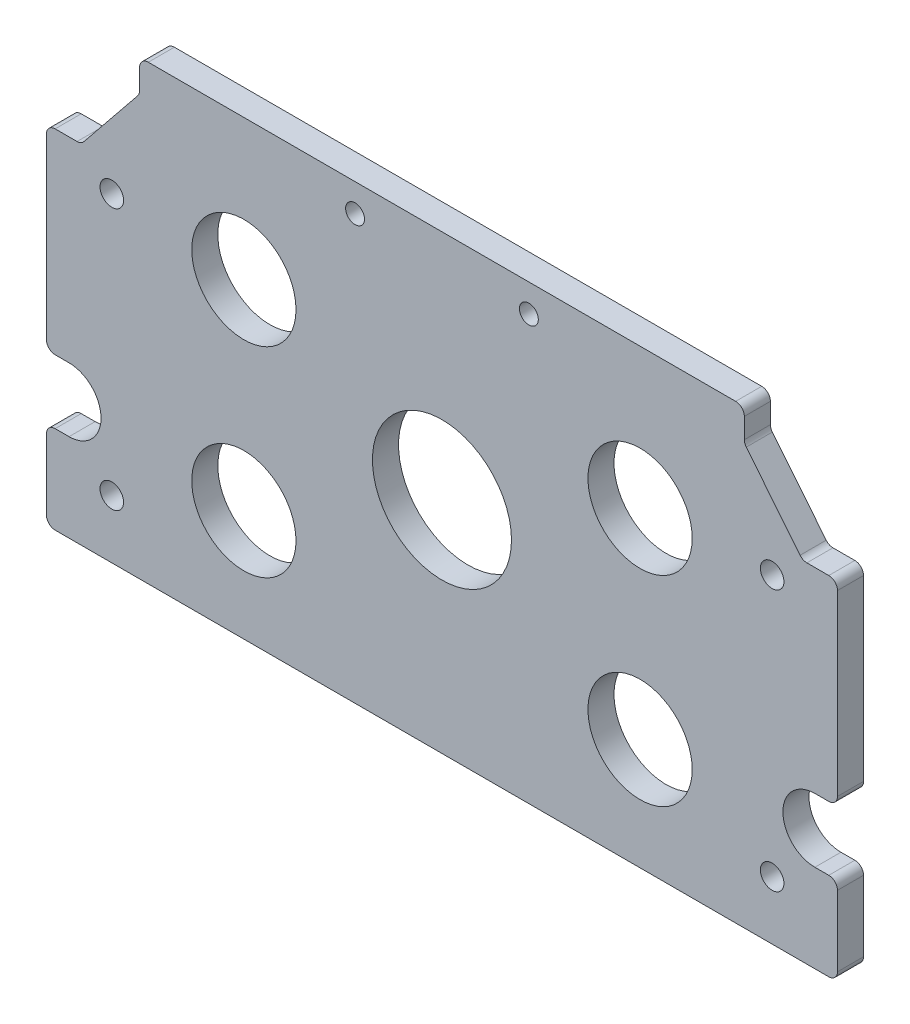
SolidWorks part; units mm, degrees
ref_plane "Front Plane" through (0, 0, 0) normal (0, 0, 1) x (1, 0, 0)
ref_plane "Top Plane" through (0, 0, 0) normal (0, 1, 0) x (1, 0, 0)
ref_plane "Right Plane" through (0, 0, 0) normal (1, 0, 0) x (0, 0, -1)
sketch "Sketch1" plane through (0, 0, 0) normal (0, 0, 1) x (1, 0, 0)
  line L32 (0.762, 54.483) -> (0.762, 41.5925)
  line L33 (2.3495, 40.005) -> (143.7005, 40.005)
  line L34 (145.288, 41.5925) -> (145.288, 54.483)
  line L35 (143.7005, 56.0705) -> (141.1605, 56.0705)
  line L36 (141.1605, 67.7545) -> (143.7005, 67.7545)
  line L37 (145.288, 69.342) -> (145.288, 101.9175)
  line L38 (143.7005, 103.505) -> (139.6964, 103.505)
  line L39 (138.4614, 104.095) -> (128.6225, 116.2765)
  line L40 (128.27, 117.274) -> (128.27, 120.9675)
  line L41 (126.6825, 122.555) -> (19.3675, 122.555)
  line L42 (17.78, 120.9675) -> (17.78, 117.274)
  line L43 (17.4275, 116.2765) -> (7.5886, 104.095)
  line L44 (6.3536, 103.505) -> (2.3495, 103.505)
  line L45 (0.762, 101.9175) -> (0.762, 69.342)
  line L46 (2.3495, 67.7545) -> (4.8895, 67.7545)
  line L47 (4.8895, 56.0705) -> (2.3495, 56.0705)
  arc A32 (2.3495, 56.0705) -> (0.762, 54.483) centre (2.3495, 54.483) ccw
  arc A33 (0.762, 41.5925) -> (2.3495, 40.005) centre (2.3495, 41.5925) ccw
  arc A34 (143.7005, 40.005) -> (145.288, 41.5925) centre (143.7005, 41.5925) ccw
  arc A35 (145.288, 54.483) -> (143.7005, 56.0705) centre (143.7005, 54.483) ccw
  arc A36 (141.1605, 67.7545) -> (141.1605, 56.0705) centre (141.1605, 61.9125) ccw
  arc A37 (143.7005, 67.7545) -> (145.288, 69.342) centre (143.7005, 69.342) ccw
  arc A38 (145.288, 101.9175) -> (143.7005, 103.505) centre (143.7005, 101.9175) ccw
  arc A39 (138.4614, 104.095) -> (139.6964, 103.505) centre (139.6964, 105.0925) ccw
  arc A40 (128.27, 117.274) -> (128.6225, 116.2765) centre (129.8575, 117.274) ccw
  arc A41 (128.27, 120.9675) -> (126.6825, 122.555) centre (126.6825, 120.9675) ccw
  arc A42 (19.3675, 122.555) -> (17.78, 120.9675) centre (19.3675, 120.9675) ccw
  arc A43 (17.4275, 116.2765) -> (17.78, 117.274) centre (16.1925, 117.274) ccw
  arc A44 (6.3536, 103.505) -> (7.5886, 104.095) centre (6.3536, 105.0925) ccw
  arc A45 (2.3495, 103.505) -> (0.762, 101.9175) centre (2.3495, 101.9175) ccw
  arc A46 (0.762, 69.342) -> (2.3495, 67.7545) centre (2.3495, 69.342) ccw
  arc A47 (4.8895, 56.0705) -> (4.8895, 67.7545) centre (4.8895, 61.9125) ccw
extrude "Boss-Extrude1" add sketch "Sketch1" along normal blind 4.7625
hole_wizard "#6 Clearance Hole1" positions "Sketch3" profile "Sketch2" hole size "#6" standard "ANSI Inch" end condition through all
sketch "Sketch3" plane through (0, 0, 4.7625) normal (0, 0, 1) x (1, 0, 0)
  line L0 (57.15, 117.475) -> (88.9, 117.475) construction
  point P0 (12.7, 98.425)
  point P6 (133.35, 98.425)
  point P8 (133.35, 50.673)
  point P10 (12.7, 50.673)
sketch "Sketch2" plane through (12.7, 98.425, 4.7625) normal (1, 0, 0) x (0, -1, 0)
  line L0 (0, 0) -> (0, 4.7625)
  line L1 (0, 4.7625) -> (2.1526, 4.7625)
  line L2 (2.1526, 4.7625) -> (2.1526, 0)
  line L5 (2.1526, 0) -> (0, 0)
  line L11 (0, -6.35) -> (0, 107.95) construction
  dimension "Thru Hole Dia." = 4.3053
  dimension "Thru Hole Depth" = 4.7625
hole_wizard "3/4 (0.75) Diameter Hole1" positions "Sketch5" profile "Sketch4" hole size "3/4" standard "ANSI Inch" end condition through all
sketch "Sketch5" plane through (0, 0, 4.7625) normal (0, 0, 1) x (1, 0, 0)
  point P0 (36.83, 96.901)
  point P2 (109.22, 96.901)
  point P4 (109.22, 60.325)
  point P6 (36.83, 60.325)
sketch "Sketch4" plane through (36.83, 96.901, 4.7625) normal (1, 0, 0) x (0, -1, 0)
  line L0 (0, 0) -> (0, 4.7625)
  line L1 (0, 4.7625) -> (9.525, 4.7625)
  line L2 (9.525, 4.7625) -> (9.525, 0)
  line L5 (9.525, 0) -> (0, 0)
  line L11 (0, -6.35) -> (0, 107.95) construction
  dimension "Thru Hole Dia." = 19.05
  dimension "Thru Hole Depth" = 4.7625
hole_wizard "1 (1) Diameter Hole1" positions "Sketch7" profile "Sketch6" hole size "1" standard "ANSI Inch" end condition through all
sketch "Sketch7" plane through (0, 0, 4.7625) normal (0, 0, 1) x (1, 0, 0)
  point P0 (73.025, 80.137)
sketch "Sketch6" plane through (73.025, 80.137, 4.7625) normal (1, 0, 0) x (0, -1, 0)
  line L0 (0, 0) -> (0, 4.7625)
  line L1 (0, 4.7625) -> (12.7, 4.7625)
  line L2 (12.7, 4.7625) -> (12.7, 0)
  line L5 (12.7, 0) -> (0, 0)
  line L11 (0, -6.35) -> (0, 107.95) construction
  dimension "Thru Hole Dia." = 25.4
  dimension "Thru Hole Depth" = 4.7625
hole_wizard "#4 Clearance Hole1" positions "Sketch9" profile "Sketch8" hole size "#4" standard "ANSI Inch" end condition through all
sketch "Sketch9" plane through (0, 0, 4.7625) normal (0, 0, 1) x (1, 0, 0)
  point P0 (57.15, 117.475)
  point P3 (88.9, 117.475)
sketch "Sketch8" plane through (57.15, 117.475, 4.7625) normal (1, 0, 0) x (0, -1, 0)
  line L0 (0, 0) -> (0, 4.7625)
  line L1 (0, 4.7625) -> (1.7272, 4.7625)
  line L2 (1.7272, 4.7625) -> (1.7272, 0)
  line L5 (1.7272, 0) -> (0, 0)
  line L11 (0, -6.35) -> (0, 107.95) construction
  dimension "Thru Hole Dia." = 3.4544
  dimension "Thru Hole Depth" = 4.7625
